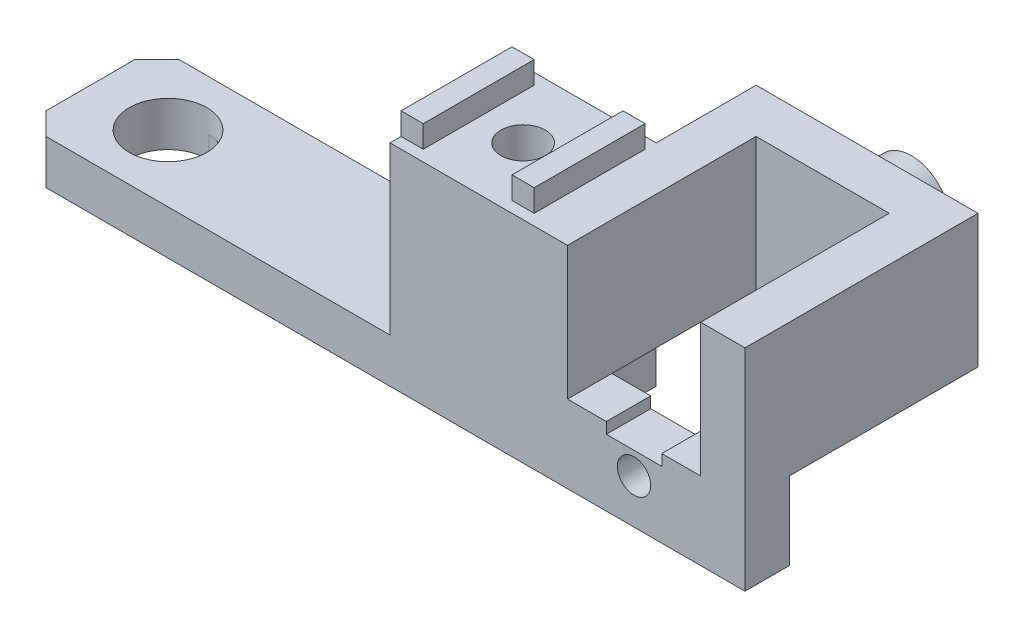
SolidWorks part; units mm, degrees
material "Plain Carbon Steel"
ref_plane "Front Plane" through (0, 0, 0) normal (0, 0, 1) x (1, 0, 0)
ref_plane "Top Plane" through (0, 0, 0) normal (0, 1, 0) x (1, 0, 0)
ref_plane "Right Plane" through (0, 0, 0) normal (1, 0, 0) x (0, 0, -1)
sketch "Sketch1" plane through (0, 0, 0) normal (0, 1, 0) x (1, 0, 0)
  line L0 (33, 6) -> (33, -6)
  line L1 (0, 6) -> (45, 6)
  line L2 (0, 6) -> (0, -6)
  line L3 (0, -6) -> (45, -6)
  line L4 (45, 6) -> (45, -6)
  line L5 (0, 0) -> (45, 0) construction
  line L14 (45, -2) -> (65, -2)
  line L15 (45, -2) -> (45, -6)
  line L16 (45, -6) -> (65, -6)
  line L17 (65, -2) -> (65, -6)
  line L18 (33, 5) -> (35, 5)
  line L19 (33, 5) -> (33, -5)
  line L20 (33, -5) -> (35, -5)
  line L21 (35, 5) -> (35, -5)
  line L22 (43, 5) -> (45, 5)
  line L23 (43, 5) -> (43, -5)
  line L24 (43, -5) -> (45, -5)
  line L25 (45, 5) -> (45, -5)
  circle A0 centre (7, 0) radius 3.5
  circle A2 centre (39.0887, 0) radius 2.1822
  dimension "D1" = 7
  dimension "D2" = 4
  dimension "D3" = 20
  dimension "D4" = 10
  dimension "D5" = 10
  dimension "D6" = 33
  dimension "D7" = 7
  dimension "D8" = 45
  dimension "D9" = 6
  dimension "D10" = 2
  dimension "D11" = 2
extrude "Boss-Extrude1" add sketch "Sketch1" along normal blind 4 contours L2 L5 A0 L0 L1 | L5 L2 L3 L0 L19 A0 region at (17.5226, 0, -3.163) region at (17.5226, 0, 3.163)
extrude "Boss-Extrude2" add sketch "Sketch1<3>" along normal blind 19 contours L5 L21 L20 L0 L3 L15 L24 L23 A2 | L21 L5 A2 L23 L22 L4 L1 L0 L18 | L0 L5 L21 L18 | L5 L19 L20 L21 | A2 L5 | L5 A2 | L23 L24 L25 L22 | L21 L20 L19 L18 region at (38.9851, 0, -3.5731) region at (34, 0, -2.5) region at (34, 0, 2.5) region at (38.9851, 0, 3.5731) region at (39.0887, 0, -0.9261) region at (39.0887, 0, 0.9261)
sketch "Sketch1<3>" plane through (0, 0, 0) normal (0, 1, 0) x (1, 0, 0) same geometry as "Sketch1"
extrude "Boss-Extrude3" add sketch "Sketch1<4>" along normal blind 7 contours L17 L14 L4 L15 L16 region at (55, 0, 4)
sketch "Sketch1<4>" plane through (0, 0, 0) normal (0, 1, 0) x (1, 0, 0) same geometry as "Sketch1"
extrude "Boss-Extrude4" add sketch "Sketch1<6>" along normal blind 2 from surface contours L5 L19 L20 L21 | L0 L5 L21 L18 | L5 L23 L24 L4 L25 | L23 L5 L4 L22 region at (34, 0, -2.5) region at (34, 0, 2.5) region at (44, 0, -2.5) region at (44, 0, 2.5) starting at face at (39, 19, 0)
sketch "Sketch1<6>" plane through (0, 0, 0) normal (0, 1, 0) x (1, 0, 0) same geometry as "Sketch1"
sketch "Sketch2" plane through (0, 7, 0) normal (0, 1, 0) x (1, 0, 0)
  line L0 (65, -2) -> (65, -6) construction
  line L2 (45, -6) -> (45, 15)
  line L3 (45, 15) -> (65, 15)
  line L4 (65, -6) -> (65, 15)
  line L6 (49, -6) -> (49, 11)
  line L7 (49, 11) -> (61, 11)
  line L8 (61, -6) -> (61, 11)
  line L9 (45, -6) -> (49, -6)
  line L10 (61, -6) -> (65, -6)
  line L11 (45, -6) -> (65, -6) construction
  dimension "D1" = 21
  dimension "D2" = 4
extrude "Boss-Extrude5" add sketch "Sketch2" along normal up to surface (12 mm away) up to face at (39, 19, 0)
sketch "Sketch4" plane through (0, 0, -15) normal (0, 0, -1) x (-1, 0, 0)
  line L0 (-65, 19) -> (-45, 7) construction
  circle A0 centre (-55, 13) radius 3.5
  dimension "D1" = 7
extrude "Boss-Extrude6" add sketch "Sketch4" along normal blind 4 contours A0 L0 | L0 A0 region at (54.2357, 14.2738, -15) region at (55.7643, 11.7262, -15)
sketch "Sketch5" plane through (0, 0, 6) normal (0, 0, 1) x (1, 0, 0)
  line L0 (49, 7) -> (61, 7) construction
  line L1 (52.5, 7) -> (57.5, 7)
  line L2 (52.5, 7) -> (52.5, 6)
  line L3 (52.5, 6) -> (57.5, 6)
  line L4 (57.5, 7) -> (57.5, 6)
  line L5 (0, 0) -> (65, 0) construction
  line L6 (55, 7) -> (55, 0) construction
  line L7 (49, 7) -> (61, 7) construction
  line L8 (55, 0) -> (55, 7) construction
  circle A0 centre (55, 4) radius 1.5
  point P14 (0, 0)
  dimension "D3" = 3
  dimension "D1" = 5
  dimension "D2" = 1
  dimension "D4" = 4
extrude "Cut-Extrude1" cut sketch "Sketch5" against normal through all
sketch "Sketch6" plane through (0, 19, 0) normal (0, 1, 0) x (1, 0, 0)
  line L0 (35, 5) -> (43, -5) construction
  circle A0 centre (39, 0) radius 2
  point P6 (0, 0)
  dimension "D1" = 4
extrude "Cut-Extrude2" cut sketch "Sketch6" against normal offset from surface 10 and the other way through all up to face at (7, 0, 3.5)
sketch "Sketch7" plane through (0, 10, 0) normal (0, 1, 0) x (1, 0, 0)
  circle A0 centre (39, 0) radius 3.5
  circle M2 centre (39, 0) radius 2
  dimension "D1" = 7
extrude "Cut-Extrude3" cut sketch "Sketch7" against normal through all contours A0 M2 | M2 | A0 region at (35.599, 10, 0) region at (39, 10, 0)
sketch "Sketch8" plane through (0, 0, 0) normal (0, -1, 0) x (1, 0, 0)
  line L0 (7.2188, 3.4932) -> (31.125, 1.9961)
  line L1 (7.2188, -3.4932) -> (31.125, -1.9961)
  arc A0 (31.125, -1.9961) -> (31.125, 1.9961) centre (31, 0) ccw
  circle A1 centre (7, 0) radius 3.5 construction
  circle A2 centre (7, 0) radius 3.5
  point P1 (0, 0)
  circle M5 centre (7, 0) radius 3.5
  dimension "D1" = 2
  dimension "D2" = 24
extrude "Cut-Extrude4" cut sketch "Sketch8" against normal blind 2 contours L1 A0 L0 M5 region at (20.1634, 0, 0)
chamfer "Chamfer1" distance 2 angle 45 2 edges at (0, 2, -6) (0, 2, 6)
